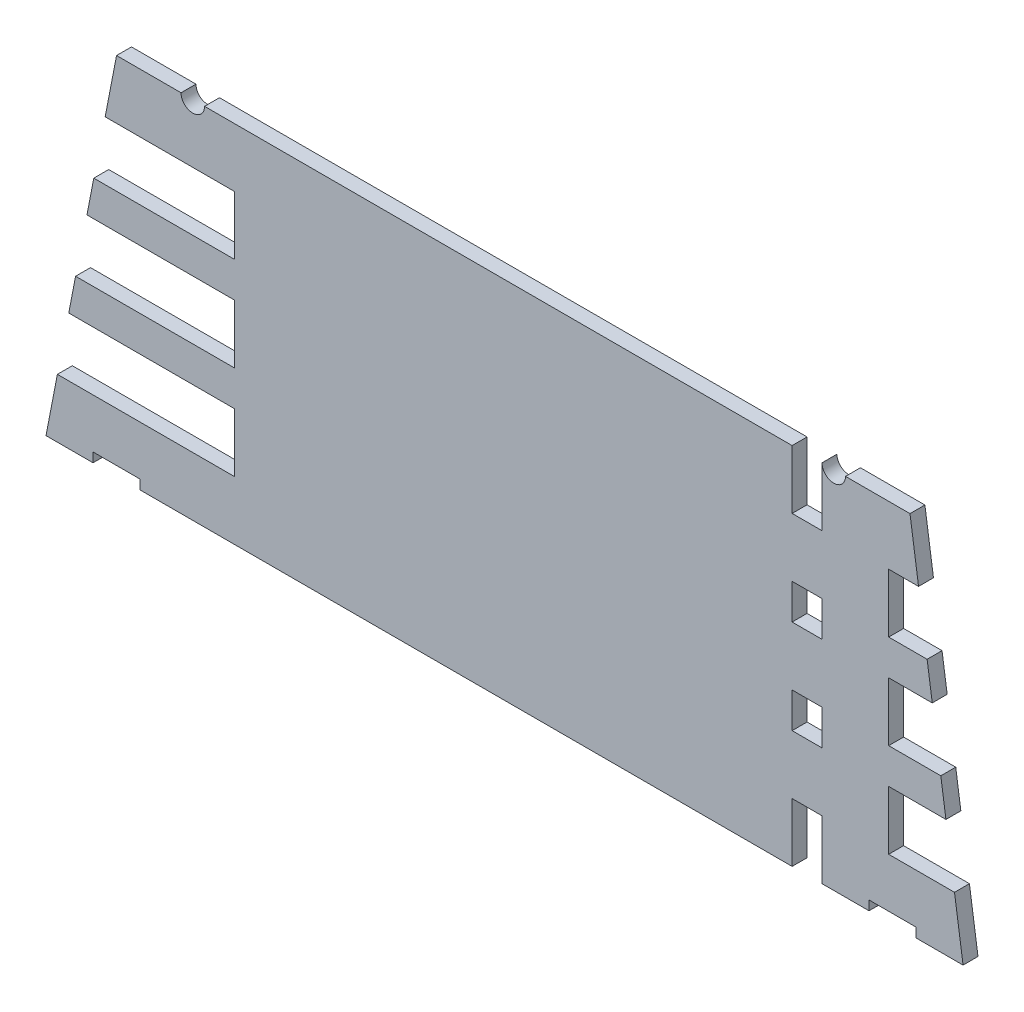
SolidWorks part; units mm, degrees
ref_plane "Front Plane" through (0, 0, 0) normal (0, 0, 1) x (1, 0, 0)
ref_plane "Top Plane" through (0, 0, 0) normal (0, 1, 0) x (1, 0, 0)
ref_plane "Right Plane" through (0, 0, 0) normal (1, 0, 0) x (0, 0, -1)
sketch "Sketch1" plane through (0, 0, 0) normal (0, 0, 1) x (1, 0, 0)
  line L0 (-152.3625, 0) -> (124.9375, 0)
  line L1 (197.6375, 0) -> (193.9964, 25)
  line L2 (175.0625, 155) -> (147.6375, 155)
  line L3 (-162.3625, 155) -> (-167.2012, 130)
  line L4 (-192.3625, 0) -> (-172.3625, 0)
  line L5 (-172.3625, 0) -> (-172.3625, 4)
  line L6 (-172.3625, 4) -> (-152.3625, 4)
  line L7 (-152.3625, 4) -> (-152.3625, 0)
  line L8 (-162.3625, 155) -> (-134.9375, 155)
  line L9 (157.6375, 0) -> (157.6375, 4)
  line L10 (157.6375, 4) -> (177.6375, 4)
  line L11 (177.6375, 4) -> (177.6375, 0)
  line L12 (177.6375, 0) -> (197.6375, 0)
  line L13 (-162.3625, 155) -> (-134.9375, 155)
  line L14 (0, 155) -> (0, 0) construction
  line L15 (-124.9375, 155) -> (124.9375, 155)
  line L16 (-167.2012, 130) -> (-112.2375, 130)
  line L17 (-112.2375, 130) -> (-112.2375, 105)
  line L18 (-112.2375, 105) -> (-172.0399, 105)
  line L19 (-174.9431, 90) -> (-112.2375, 90)
  line L20 (-112.2375, 90) -> (-112.2375, 65)
  line L21 (-112.2375, 65) -> (-179.7819, 65)
  line L22 (-182.6851, 50) -> (-112.2375, 50)
  line L23 (-112.2375, 50) -> (-112.2375, 25)
  line L24 (-112.2375, 25) -> (-187.5238, 25)
  line L25 (-172.0399, 105) -> (-174.9431, 90)
  line L26 (-179.7819, 65) -> (-182.6851, 50)
  line L27 (-187.5238, 25) -> (-192.3625, 0)
  line L28 (124.9375, 90) -> (124.9375, 105)
  line L29 (124.9375, 105) -> (137.6375, 105)
  line L30 (137.6375, 105) -> (137.6375, 90)
  line L31 (137.6375, 90) -> (124.9375, 90)
  line L32 (-112.2375, 105) -> (-112.2375, 90) construction
  line L33 (124.9375, 50) -> (124.9375, 65)
  line L34 (124.9375, 65) -> (137.6375, 65)
  line L35 (137.6375, 65) -> (137.6375, 50)
  line L36 (137.6375, 50) -> (124.9375, 50)
  line L37 (137.6375, 0) -> (137.6375, 25)
  line L38 (137.6375, 25) -> (124.9375, 25)
  line L39 (124.9375, 25) -> (124.9375, 0)
  line L40 (124.9375, 155) -> (124.9375, 130)
  line L41 (124.9375, 130) -> (137.6375, 130)
  line L42 (137.6375, 130) -> (137.6375, 155)
  line L43 (137.6375, 0) -> (157.6375, 0)
  line L44 (178.7036, 130) -> (166.0036, 130)
  line L45 (166.0036, 130) -> (166.0036, 105)
  line L46 (166.0036, 105) -> (182.3448, 105)
  line L47 (184.5294, 90) -> (166.0036, 90)
  line L48 (166.0036, 90) -> (166.0036, 65)
  line L49 (166.0036, 65) -> (188.1706, 65)
  line L50 (190.3552, 50) -> (166.0036, 50)
  line L51 (166.0036, 50) -> (166.0036, 25)
  line L52 (166.0036, 25) -> (193.9964, 25)
  line L53 (190.3552, 50) -> (188.1706, 65)
  line L54 (184.5294, 90) -> (182.3448, 105)
  line L55 (178.7036, 130) -> (175.0625, 155)
  arc A0 (-134.9375, 155) -> (-124.9375, 155) centre (-129.9375, 155) ccw
  arc A1 (147.6375, 155) -> (137.6375, 155) centre (142.6375, 155) cw
  dimension "D2" = 20
  dimension "D3" = 20
  dimension "D4" = 282.575
  dimension "D5" = 15
  dimension "D6" = 10
  dimension "D7" = 12.7
  dimension "D8" = 4
  dimension "D9" = 10
  dimension "D10" = 310
  dimension "D11" = 5
  dimension "D12" = 25
  dimension "D13" = 12.7
  dimension "D14" = 25
  dimension "D15" = 12.7
  dimension "D16" = 155
extrude "Extrude1" add sketch "Sketch1" along normal blind 6.35 contours L0 L15 A0 L8 L3 L4 L5 L6 L7 | L0 L9 L10 L11 L12 L1 L2 A1 L15 region at (11.4062, 76.0498, 0)
